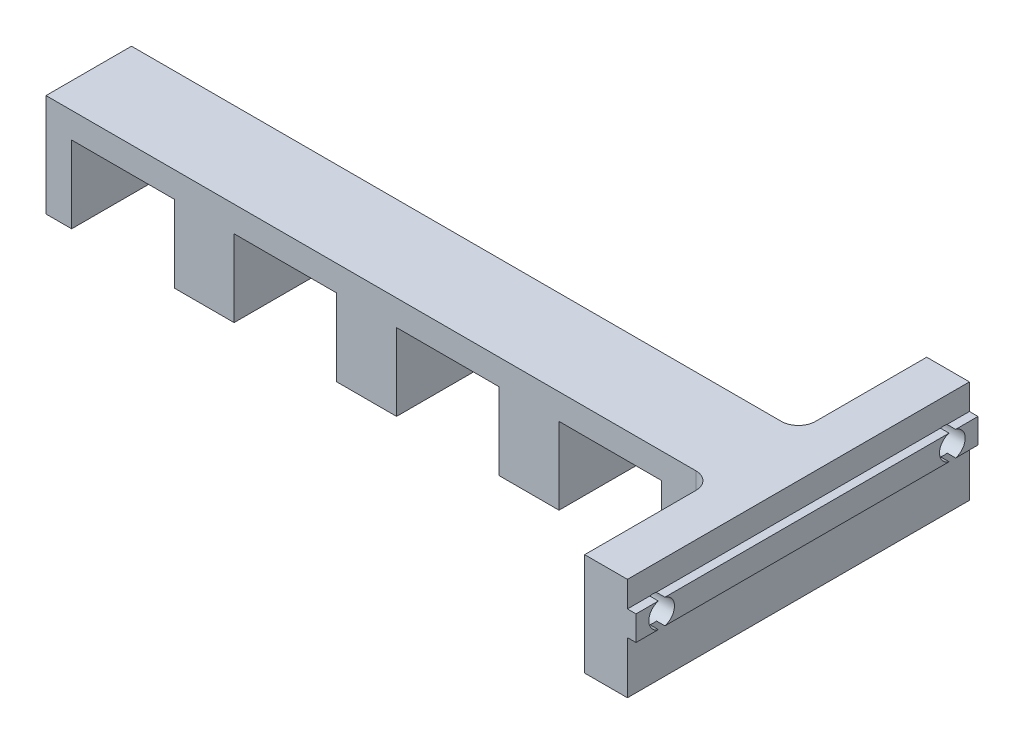
SolidWorks part; units mm, degrees
ref_plane "Front Plane" through (0, 0, 0) normal (0, 0, 1) x (1, 0, 0)
ref_plane "Top Plane" through (0, 0, 0) normal (0, 1, 0) x (1, 0, 0)
ref_plane "Right Plane" through (0, 0, 0) normal (1, 0, 0) x (0, 0, -1)
sketch "Esquisse1" plane through (0, 0, 0) normal (0, 0, 1) x (1, 0, 0)
  line L0 (3, 0) -> (3, 9)
  line L1 (3, 9) -> (15, 9)
  line L2 (15, 9) -> (15, 0)
  line L3 (15, 0) -> (22, 0)
  line L4 (22, 0) -> (22, 9)
  line L5 (22, 9) -> (34, 9)
  line L6 (34, 9) -> (34, 0)
  line L7 (34, 0) -> (41, 0)
  line L8 (41, 0) -> (41, 9)
  line L9 (41, 9) -> (53, 9)
  line L10 (53, 9) -> (53, 0)
  line L11 (53, 0) -> (60, 0)
  line L12 (83, 0) -> (83, 12)
  line L13 (83, 12) -> (0, 12)
  line L14 (0, 12) -> (0, 0)
  line L15 (0, 0) -> (3, 0)
  line L16 (60, 0) -> (60, 9)
  line L17 (60, 9) -> (72, 9)
  line L18 (72, 9) -> (72, 0)
  line L19 (72, 0) -> (83, 0)
  point P20 (51.6644, 9)
  dimension "D1" = 83
  dimension "D2" = 12
  dimension "D3" = 12
  dimension "D4" = 12
  dimension "D5" = 3
  dimension "D6" = 12
  dimension "D7" = 12
  dimension "D8" = 3
  dimension "D9" = 7
  dimension "D10" = 7
  dimension "D11" = 7
extrude "Main" add sketch "Esquisse1" along normal mid plane 10
sketch "Sketch1" plane through (0, 0, 0) normal (0, 0, 1) x (1, 0, 0)
  line L0 (78, 12) -> (83, 12)
  line L1 (83, 12) -> (0, 12) construction
  line L2 (83, 12) -> (83, 9)
  line L3 (83, 0) -> (83, 12) construction
  line L4 (83, 9) -> (84, 9)
  line L5 (84, 9) -> (84, 6.1)
  line L6 (84, 6.1) -> (83, 6.1)
  line L7 (83, 6.1) -> (83, 0)
  line L8 (83, 0) -> (78, 0)
  line L9 (72, 0) -> (83, 0) construction
  line L10 (78, 0) -> (78, 12)
  dimension "D1" = 5
  dimension "D2" = 2.9
  dimension "D3" = 3
  dimension "D4" = 1
extrude "MakerBeamFix" add sketch "Sketch1" along normal mid plane 40
sketch "Sketch2" plane through (84, 0, 0) normal (1, 0, 0) x (0, 0, -1)
  line L0 (-20, 6.1) -> (-20, 9) construction
  line L1 (20, 6.1) -> (20, 9) construction
  circle A0 centre (-17, 7.55) radius 1.5
  circle A1 centre (17, 7.55) radius 1.5
  point P4 (-20, 7.55)
  dimension "D3" = 3
  dimension "D1" = 3
  dimension "D2" = 3
  dimension "D4" = 34
extrude "MakerBeamFixHole" cut sketch "Sketch2" against normal blind 30
fillet "Fillet1" radius 2 2 edges at (78, 6, -5) (78, 6, 5)
